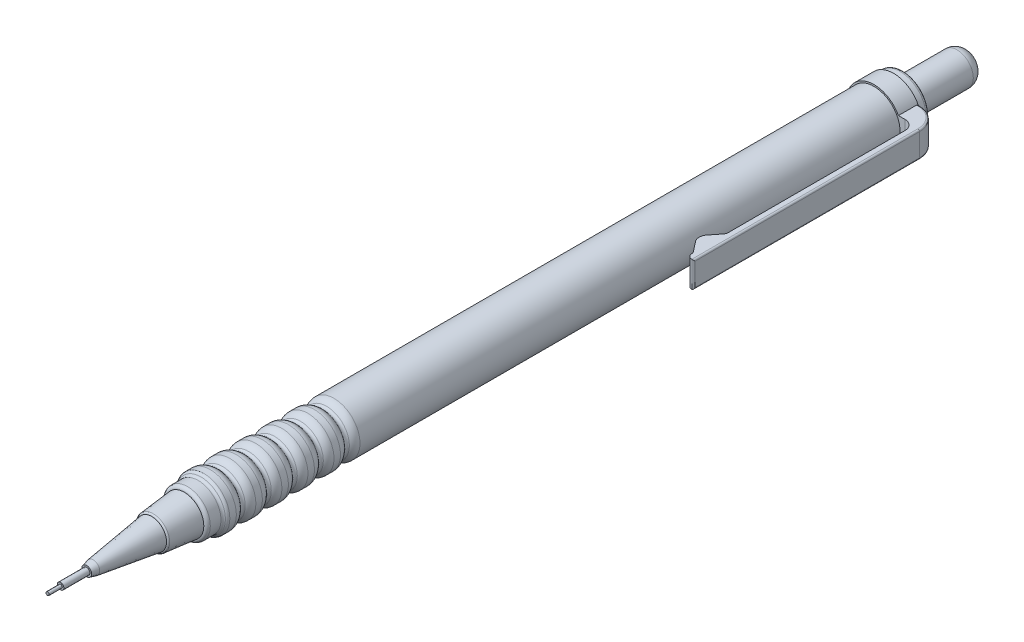
SolidWorks part; units mm, degrees
material "1060 Alloy"
ref_plane "Front Plane" through (0, 0, 0) normal (0, 0, 1) x (1, 0, 0)
ref_plane "Top Plane" through (0, 0, 0) normal (0, 1, 0) x (1, 0, 0)
ref_plane "Right Plane" through (0, 0, 0) normal (1, 0, 0) x (0, 0, -1)
sketch "Sketch1" plane through (0, 0, 0) normal (0, 0, 1) x (1, 0, 0)
  circle A0 centre (0, 0) radius 4
  dimension "D1" = 8
extrude "Boss-Extrude1" add sketch "Sketch1" along normal blind 89
fillet "Fillet2" radius 0.5 1 edges at (4, 0, 0)
fillet "Fillet3" radius 1.5 1 edges at (4, 0, 89)
sketch "Sketch2" plane through (0, 0, 89) normal (0, 0, 1) x (1, 0, 0)
  circle A0 centre (0, 0) radius 4
  dimension "D1" = 8
extrude "Boss-Extrude2" add sketch "Sketch2" along normal blind 4
fillet "Fillet4" radius 1.5 1 edges at (4, 0, 89)
fillet "Fillet5" radius 1.5 1 edges at (4, 0, 93)
sketch "Sketch3" plane through (0, 0, 93) normal (0, 0, 1) x (1, 0, 0)
  circle A0 centre (0, 0) radius 4
  dimension "D1" = 8
extrude "Boss-Extrude3" add sketch "Sketch3" along normal blind 4
fillet "Fillet6" radius 1.5 1 edges at (4, 0, 97)
sketch "Sketch4" plane through (0, 0, 97) normal (0, 0, 1) x (1, 0, 0)
  circle A0 centre (0, 0) radius 4
  dimension "D1" = 8
extrude "Boss-Extrude4" add sketch "Sketch4" along normal blind 4
fillet "Fillet7" radius 1.5 1 edges at (4, 0, 101)
sketch "Sketch5" plane through (0, 0, 101) normal (0, 0, 1) x (1, 0, 0)
  circle A0 centre (0, 0) radius 4
  dimension "D1" = 8
extrude "Boss-Extrude5" add sketch "Sketch5" along normal blind 4
fillet "Fillet8" radius 1.5 1 edges at (4, 0, 93)
fillet "Fillet9" radius 1.5 1 edges at (4, 0, 97)
fillet "Fillet10" radius 1.5 1 edges at (4, 0, 101)
fillet "Fillet11" radius 1.5 1 edges at (4, 0, 105)
sketch "Sketch6" plane through (0, 0, 105) normal (0, 0, 1) x (1, 0, 0)
  circle A0 centre (0, 0) radius 4
  dimension "D1" = 8
extrude "Boss-Extrude6" add sketch "Sketch6" along normal blind 3
fillet "Fillet12" radius 1.5 1 edges at (4, 0, 105)
fillet "Fillet13" radius 0.5 1 edges at (2.5, 0, 105)
fillet "Fillet14" radius 0.5 4 edges at (2.5, 0, 101) (2.5, 0, 89) (2.5, 0, 93) (2.5, 0, 97)
fillet "Fillet15" radius 0.5 1 edges at (4, 0, 108)
sketch "Sketch7" plane through (0, 0, 108) normal (0, 0, 1) x (1, 0, 0)
  circle A0 centre (0, 0) radius 3.5
extrude "Boss-Extrude7" add sketch "Sketch7" along normal blind 2.5
fillet "Fillet16" radius 0.5 1 edges at (3.5, 0, 108)
fillet "Fillet17" radius 0.5 1 edges at (3.5, 0, 110.5)
sketch "Sketch8" plane through (0, 0, 110.5) normal (0, 0, 1) x (1, 0, 0)
  circle A0 centre (0, 0) radius 3
  dimension "D1" = 6
extrude "Boss-Extrude8" add sketch "Sketch8" along normal blind 5
chamfer "Chamfer1" distance 5 distance2 0.5 1 edges at (3, 0, 115.5) first distance on face at (3, 0, 115.5)
fillet "Fillet18" radius 0.25 1 edges at (2.5, 0, 115.5)
sketch "Sketch10" plane through (0, 0, 115.5) normal (0, 0, 1) x (1, 0, 0)
  circle A0 centre (0, 0) radius 2.2738
extrude "Boss-Extrude9" add sketch "Sketch10" along normal blind 9
chamfer "Chamfer2" distance 9 distance2 1.27 1 edges at (2.2738, 0, 124.5) first distance on face at (2.2738, 0, 124.5)
sketch "Sketch13" plane through (0, 0, 124.5) normal (0, 0, 1) x (1, 0, 0)
  circle A0 centre (0, 0) radius 1.0038
extrude "Boss-Extrude10" add sketch "Sketch13" along normal blind 1
chamfer "Chamfer3" distance 1 distance2 0.25 1 edges at (1.0038, 0, 125.5) first distance on face at (1.0038, 0, 125.5)
sketch "Sketch14" plane through (0, 0, 125.5) normal (0, 0, 1) x (1, 0, 0)
  circle A0 centre (0, 0) radius 0.5
  dimension "D1" = 1
extrude "Boss-Extrude11" add sketch "Sketch14" along normal blind 4
sketch "Sketch15" plane through (0, 0, 129.5) normal (0, 0, 1) x (1, 0, 0)
  circle A0 centre (0, 0) radius 0.25
  dimension "D1" = 0.5
extrude "Boss-Extrude13" add sketch "Sketch15" along normal blind 2
ref_plane "Plane1" through (0, 0, 1.5) normal (0, 0, -1) x (-1, 0, 0)
sketch "Sketch16" plane through (0, 0, 1.5) normal (0, 0, -1) x (-1, 0, 0)
  circle A0 centre (0, 0) radius 4.25
  dimension "D1" = 8.5
extrude "Boss-Extrude14" add sketch "Sketch16" against normal blind 3
sketch "Sketch17" plane through (0, 0, 0) normal (0, 0, -1) x (-1, 0, 0)
  circle A0 centre (0, 0) radius 2.5
  dimension "D1" = 5
extrude "Boss-Extrude15" add sketch "Sketch17" along normal blind 10
sketch "Sketch18" plane through (0, 0, 1.5) normal (0, 0, -1) x (-1, 0, 0)
  line L1 (-3.75, 2) -> (-7.25, 2)
  line L2 (-3.75, 2) -> (-3.75, -2)
  line L3 (-3.75, -2) -> (-7.25, -2)
  line L4 (-7.25, 2) -> (-7.25, -2)
  dimension "D1" = 4
  dimension "D2" = 3.5
  dimension "D3" = 3.75
  dimension "D4" = 2
extrude "Boss-Extrude16" add sketch "Sketch18" against normal blind 3
sketch "Sketch19" plane through (0, 0, 1.5) normal (0, 0, -1) x (-1, 0, 0)
  line L0 (-7.25, -2) -> (-3.75, -2) construction
  line L1 (-7.25, 2) -> (-6.25, 2)
  line L2 (-7.25, 2) -> (-7.25, -2)
  line L3 (-7.25, -2) -> (-6.25, -2)
  line L4 (-6.25, 2) -> (-6.25, -2)
  dimension "D1" = 1
extrude "Boss-Extrude17" add sketch "Sketch19" against normal blind 38
fillet "Fillet20" radius 3.25 1 edges at (7.25, 0, 1.5)
fillet "Fillet21" radius 1.75 1 edges at (-2.5, 0, -10)
fillet "Fillet22" radius 1.5 1 edges at (6.25, 0, 4.5)
fillet "Fillet23" radius 0.25 7 edges at (3.875, 2, 1.5) (6.2981, 2, 2.4519) (3.875, -2, 1.5) (6.2981, -2, 2.4519) (7.25, 0, 39.5) (7.25, 2, 22.125) (7.25, -2, 22.125)
sketch "Sketch20" plane through (0, 2, 0) normal (0, 1, 0) x (1, 0, 0)
  line L0 (6.25, -39.5) -> (7, -39.5) construction
  line L1 (4, -32.5) -> (7, -32.5)
  line L2 (4, -32.5) -> (4, -39.5)
  line L3 (4, -39.5) -> (7, -39.5)
  line L4 (7, -32.5) -> (7, -39.5)
  line L5 (7, -39.5) -> (7, -4.75) construction
  line L6 (7, -39.5) -> (4.6376, -36.5)
  line L7 (4, -35.5) -> (4, -36.5)
  line L8 (4.6376, -36.5) -> (4.6376, -35.5)
  line L9 (4.6376, -35.5) -> (7, -32.5)
  line M6 (6.25, -6) -> (6.25, -39.5)
  dimension "D1" = 7
  dimension "D2" = 3
  dimension "D3" = 3
  dimension "D4" = 1
extrude "Boss-Extrude20" add sketch "Sketch20" against normal blind 4 contours L9 L8 L6 M6 region at (5.6244, 2, 36)
fillet "Fillet24" radius 0.75 1 edges at (6.25, 0, 39.5)
fillet "Fillet25" radius 0.75 1 edges at (6.25, 0, 38.5476)
fillet "Fillet26" radius 0.75 1 edges at (6.25, 0, 33.4524)
fillet "Fillet28" radius 1.25 1 edges at (4.6376, 0, 36.5)
fillet "Fillet29" radius 1.25 1 edges at (4.6376, 0, 35.5)
